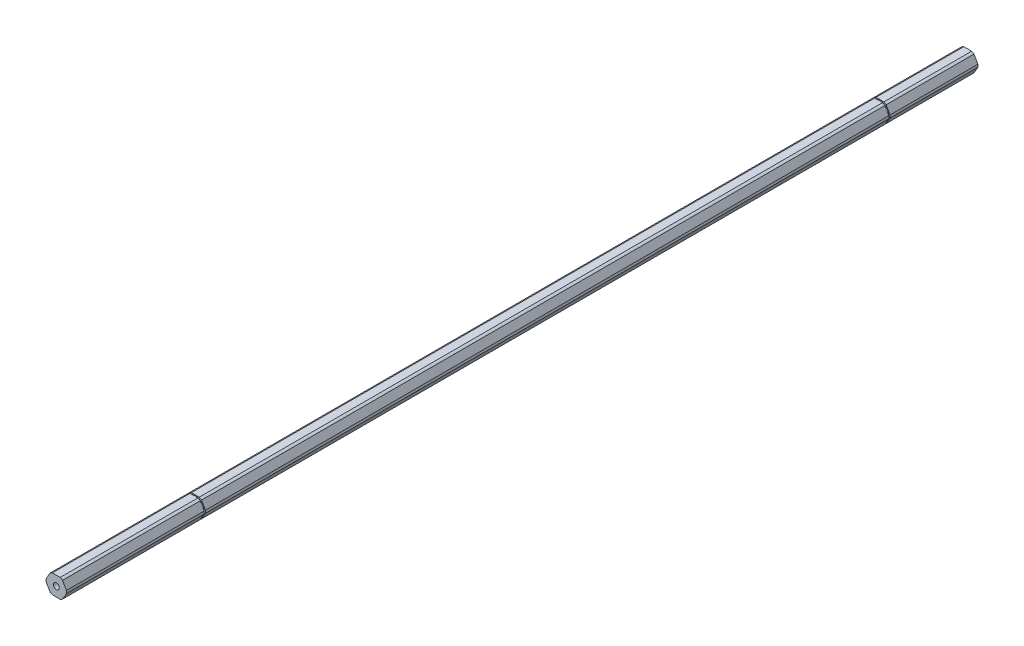
SolidWorks part; units mm, degrees
material "6061-T6 (SS)"
ref_plane "Front Plane" through (0, 0, 0) normal (0, 0, 1) x (1, 0, 0)
ref_plane "Top Plane" through (0, 0, 0) normal (0, 1, 0) x (1, 0, 0)
ref_plane "Right Plane" through (0, 0, 0) normal (1, 0, 0) x (0, 0, -1)
sketch "Sketch1" plane through (0, 0, 0) normal (0, 0, 1) x (1, 0, 0)
  line L1 (3.6662, 6.35) -> (-3.6662, 6.35)
  line L2 (-3.6662, 6.35) -> (-7.3323, 0)
  line L3 (-7.3323, 0) -> (-3.6662, -6.35)
  line L4 (-3.6662, -6.35) -> (3.6662, -6.35)
  line L5 (3.6662, -6.35) -> (7.3323, 0)
  line L6 (7.3323, 0) -> (3.6662, 6.35)
  circle A0 centre (0, 0) radius 6.35 construction
  circle A1 centre (0, 0) radius 6.875
  circle A2 centre (0, 0) radius 2
  point P1 (0, 6.35)
  dimension "D2" = 13.75
  dimension "D3" = 4
  dimension "D1" = 12.7
extrude "Boss-Extrude1" add sketch "Sketch1" along normal blind 609.6 contours L6 A1 L1 L2 L3 L4 L5 A2 region at (3.3439, 5.7918, 0)
sketch "Sketch2" plane through (0, 0, 0) normal (0, 1, 0) x (1, 0, 0)
  line L0 (2.635, -609.6) -> (-2.635, -609.6) construction
  line L1 (-5.8547, -516.636) -> (5.8547, -516.636) construction
  line L2 (-5.8547, -516.636) -> (-5.8547, -517.525)
  line L3 (-5.8547, -517.525) -> (5.8547, -517.525) construction
  line L4 (5.8547, -516.636) -> (5.8547, -517.525)
  line L5 (0, -609.6) -> (0, 0) construction
  line L6 (7.5057, -516.636) -> (-7.5057, -516.636)
  line L7 (7.5057, -516.636) -> (7.5057, -517.525)
  line L8 (7.5057, -517.525) -> (-7.5057, -517.525)
  line L9 (-7.5057, -516.636) -> (-7.5057, -517.525)
  line L10 (2.635, 0) -> (-2.635, 0) construction
  line L11 (-5.8547, -58.7375) -> (5.8547, -58.7375)
  line L12 (-5.8547, -58.7375) -> (-5.8547, -59.6265)
  line L13 (-5.8547, -59.6265) -> (5.8547, -59.6265)
  line L14 (5.8547, -58.7375) -> (5.8547, -59.6265)
  line L16 (5.8547, -58.7375) -> (7.5057, -58.7375)
  line L17 (5.8547, -58.7375) -> (5.8547, -59.6265)
  line L18 (5.8547, -59.6265) -> (7.5057, -59.6265)
  line L19 (7.5057, -58.7375) -> (7.5057, -59.6265)
  point P6 (0, -609.6)
  point P7 (0, -517.525)
  point P21 (0, -58.7375)
  dimension "D1" = 92.075
  dimension "D2" = 0.889
  dimension "D3" = 11.7094
  dimension "D4" = 1.651
  dimension "D5" = 1.651
  dimension "D6" = 58.7375
  dimension "D7" = 0.889
  dimension "D8" = 11.7094
  dimension "D9" = 1.651
revolve "Cut-Revolve1" cut sketch "Sketch2" angle 360 about L5 region at (6.6802, 0, 517.0805) region at (6.6802, 0, 59.182)
equation "\"D2@Sketch1\"=13.750000mm"
equation "\"D3@Sketch1\"=4mm"
equation "\"D5@Sketch2\"=\"D4@Sketch2\""
equation "\"D3@Sketch2\"=\"D8@Sketch2\""
